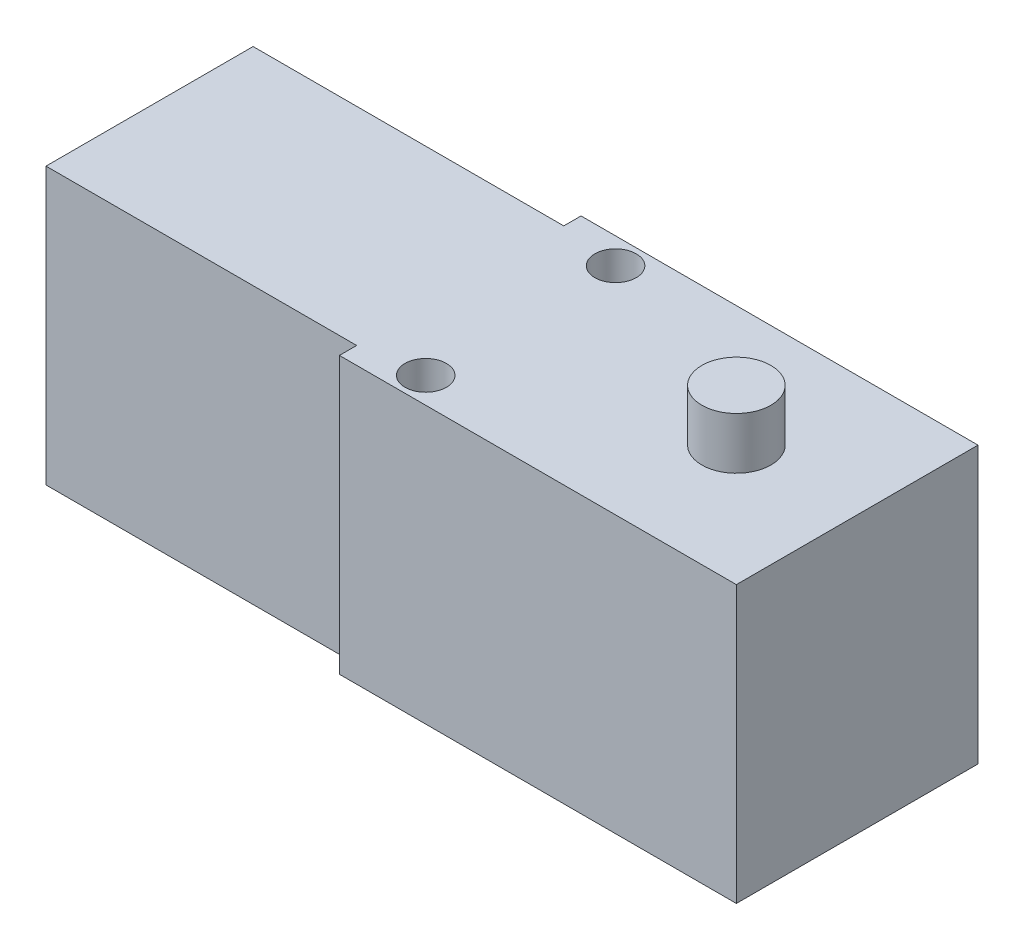
SolidWorks part; units mm, degrees
ref_plane "Front Plane" through (0, 0, 0) normal (0, 0, 1) x (1, 0, 0)
ref_plane "Top Plane" through (0, 0, 0) normal (0, 1, 0) x (1, 0, 0)
ref_plane "Right Plane" through (0, 0, 0) normal (1, 0, 0) x (0, 0, -1)
sketch "Sketch1" plane through (0, 0, 0) normal (0, 1, 0) x (1, 0, 0)
  line L0 (-28.575, 0) -> (36.5125, 0) construction
  line L1 (-28.575, -9.525) -> (0, -9.525)
  line L2 (-28.575, -9.525) -> (-28.575, 9.525)
  line L3 (-28.575, 9.525) -> (0, 9.525)
  line L4 (0, -9.525) -> (0, 9.525)
  line L5 (-28.575, -9.525) -> (0, 9.525) construction
  line L6 (-28.575, 9.525) -> (0, -9.525) construction
  line L7 (36.5125, -11.1125) -> (0, -11.1125)
  line L8 (36.5125, -11.1125) -> (36.5125, 11.1125)
  line L9 (36.5125, 11.1125) -> (0, 11.1125)
  line L10 (0, -11.1125) -> (0, 11.1125)
  line L11 (36.5125, -11.1125) -> (0, 11.1125) construction
  line L12 (36.5125, 11.1125) -> (0, -11.1125) construction
  point P0 (-14.2875, 0)
  point P5 (18.2563, 0)
  dimension "D1" = 28.575
  dimension "D2" = 36.5125
  dimension "D3" = 22.225
  dimension "D4" = 19.05
extrude "Boss-Extrude1" add sketch "Sketch1" along normal mid plane 25.4 contours L1 L4 L3 L2 | L10 L7 L8 L9 L4 region at (-14.2875, 0, 0) region at (18.2563, 0, 0)
sketch "Sketch2" plane through (0, 0, 0) normal (0, -1, 0) x (1, 0, 0)
  line L0 (36.5125, 11.1125) -> (36.5125, -11.1125) construction
  circle A0 centre (25.4, 0) radius 3.175
  point P5 (36.5125, 0)
  dimension "D1" = 6.35
  dimension "D2" = 11.1125
extrude "Boss-Extrude2" add sketch "Sketch2" along normal mid plane 34.925
sketch "Sketch3" plane through (0, -12.7, 0) normal (0, -1, 0) x (1, 0, 0)
  line L0 (0, -9.525) -> (0, -11.1125) construction
  line L1 (5.5562, -8.7312) -> (5.5562, 8.7312) construction
  circle A0 centre (5.5562, 8.7312) radius 1.905
  circle A1 centre (5.5562, -8.7312) radius 1.905
  point P7 (25.4, 0)
  point P10 (5.5562, 0)
  dimension "D1" = 3.81
  dimension "D2" = 17.4625
  dimension "D3" = 5.5562
extrude "Cut-Extrude1" cut sketch "Sketch3" against normal through all
